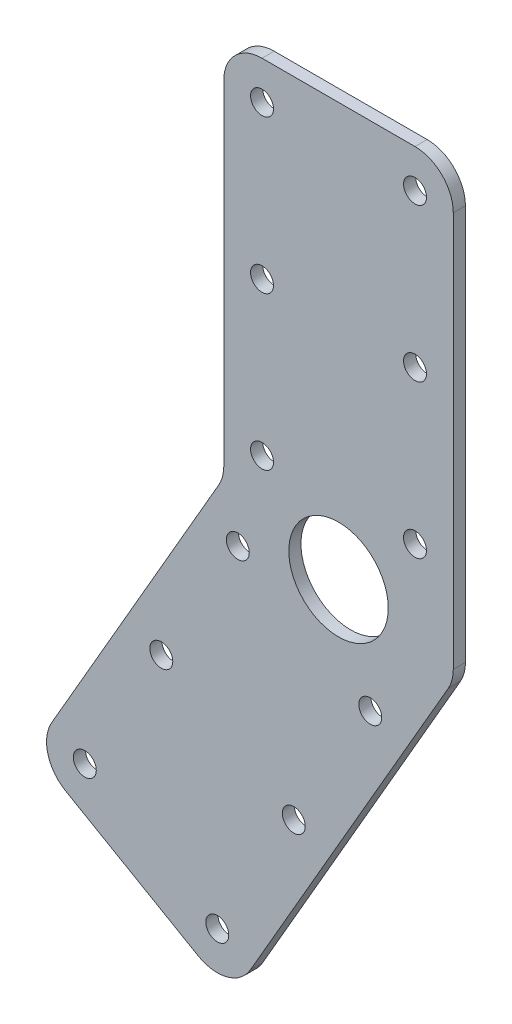
SolidWorks part; units mm, degrees
material "6061 Alloy"
ref_plane "Front Plane" through (0, 0, 0) normal (0, 0, 1) x (1, 0, 0)
ref_plane "Top Plane" through (0, 0, 0) normal (0, 1, 0) x (1, 0, 0)
ref_plane "Right Plane" through (0, 0, 0) normal (1, 0, 0) x (0, 0, -1)
sketch "Sketch1" plane through (0, 0, 0) normal (0, 0, 1) x (1, 0, 0)
  line L0 (0, 0) -> (0, 50)
  line L1 (0, 50) -> (30, 50)
  line L2 (30, 50) -> (30, -8.0385)
  line L3 (30, -8.0385) -> (0.9808, -58.3013)
  line L4 (0.9808, -58.3013) -> (-25, -43.3013)
  line L5 (-25, -43.3013) -> (0, 0)
  line L6 (0, 0) -> (30, -8.0385) construction
  line L7 (5, 50) -> (5, 0) construction
  line L8 (0, 0) -> (5, 0) construction
  line L9 (5, 45) -> (5, 50) construction
  line L10 (15, 50) -> (15, -4.0192) construction
  line L11 (-20.6699, -45.8013) -> (4.3301, -2.5) construction
  line L12 (0, 0) -> (4.3301, -2.5) construction
  line L13 (0, 25) -> (5, 25) construction
  line L14 (-12.5, -21.6506) -> (-8.1699, -24.1506) construction
  line L15 (-12.0096, -50.8013) -> (15, -4.0192) construction
  line L16 (15, -4.0192) -> (10.4904, -11.8301) construction
  line L17 (10.4904, -11.8301) -> (19.1506, -16.8301) construction
  circle A0 centre (15, -4.0192) radius 6.5
  circle A1 centre (5, 45) radius 1.5
  circle A2 centre (5, 25) radius 1.5
  circle A3 centre (5, 5) radius 1.5
  circle A4 centre (25, 5) radius 1.5
  circle A5 centre (25, 25) radius 1.5
  circle A6 centre (25, 45) radius 1.5
  circle A7 centre (-18.1699, -41.4711) radius 1.5
  circle A8 centre (-8.1699, -24.1506) radius 1.5
  circle A9 centre (1.8301, -6.8301) radius 1.5
  circle A10 centre (19.1506, -16.8301) radius 1.5
  circle A11 centre (9.1506, -34.1506) radius 1.5
  circle A12 centre (-0.8494, -51.4711) radius 1.5
  dimension "D5" = 13
  dimension "D7" = 3
  dimension "D9" = 20
  dimension "D10" = 20
  dimension "D11" = 5
  dimension "D1" = 30
  dimension "D2" = 50
  dimension "D3" = 50
  dimension "D4" = 150
  dimension "D6" = 5
  dimension "D8" = 5
  dimension "D12" = 20
  dimension "D13" = 20
extrude "Boss-Extrude1" add sketch "Sketch1" along normal blind 1.5875
fillet "Fillet1" radius 5 6 edges at (30, -8.0385, 0.7937) (0, 0, 0.7937) (0.9808, -58.3013, 0.7937) (-25, -43.3013, 0.7937) (0, 50, 0.7937) (30, 50, 0.7937)
